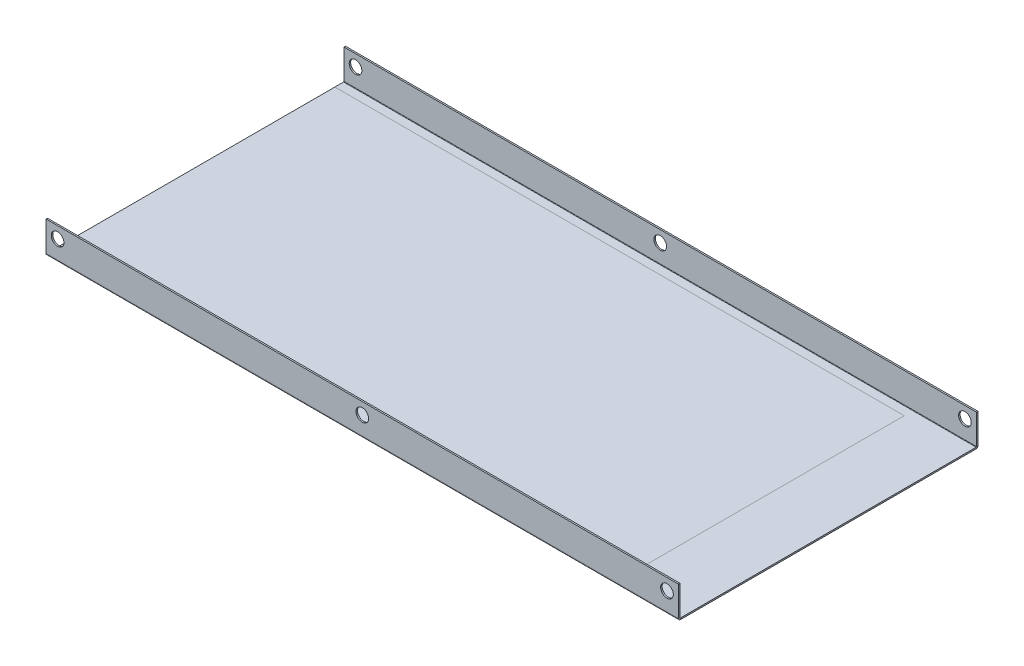
SolidWorks part; units mm, degrees
note: The reader was unsure of these and kept them because the rebuilt part matched: thickness of "基体-法兰1", "边线-法兰1", "钣金8", "钣金9", "钣金10", "钣金11"; flange length of "边线-法兰1".
material "1023 碳钢板 (SS)"
ref_plane "前视基准面" through (0, 0, 0) normal (0, 0, 1) x (1, 0, 0)
ref_plane "上视基准面" through (0, 0, 0) normal (0, 1, 0) x (1, 0, 0)
ref_plane "右视基准面" through (0, 0, 0) normal (1, 0, 0) x (0, 0, -1)
sketch "草图1" plane through (0, 0, 0) normal (0, 1, 0) x (1, 0, 0)
  line L1 (-150, -71) -> (150, -71)
  line L2 (-150, -71) -> (-150, 71)
  line L3 (-150, 71) -> (150, 71)
  line L4 (150, -71) -> (150, 71)
  line L5 (-150, -71) -> (150, 71) construction
  line L6 (-150, 71) -> (150, -71) construction
  point P0 (0, 0)
  dimension "D1" = 142
  dimension "D2" = 300
base flange "基体-法兰1" sketch "草图1" thickness 0.7 reverse thickness direction no parameters "D1"=0.2
edge flange "边线-法兰1" sketch "草图15" flange profiles "草图15", "草图16" flange angle 90 flange length 15 flange position material inside bend radius 0.2 thickness 0.7 relief rectangular parameters "D6"=10, "D8"=1
sketch "草图15" plane through (0, 0, -71) normal (0, 0, -1) x (-1, 0, 0)
  line L2 (-150, 0) -> (-150, 14.3)
  line L3 (-150, 14.3) -> (150, 14.3)
  line L4 (150, 14.3) -> (150, 0)
  line L11 (-150, 0) -> (150, 0) construction
  line L12 (-150, 0) -> (150, 0)
sketch "草图16" plane through (0, 0, 71) normal (0, 0, 1) x (1, 0, 0)
  line L2 (-150, 0) -> (-150, 14.3)
  line L3 (-150, 14.3) -> (150, 14.3)
  line L4 (150, 14.3) -> (150, 0)
  line L7 (-150, 0) -> (150, 0) construction
  line L8 (-150, 0) -> (150, 0)
bend "边线折弯1" bend radius 0.2 bend angle 90 parameters "D5"=1
bend "边线折弯2" bend radius 0.2 bend angle 90 parameters "D5"=2
sketch "草图18" plane through (0, 0, -71) normal (0, 0, -1) x (-1, 0, 0)
  line L0 (-150, 14.3) -> (-150, 0.2) construction
  line L1 (150, 14.3) -> (-150, 14.3) construction
  line L2 (0, 14.3) -> (0, 0) construction
  circle A0 centre (-144.5, 8.8) radius 3
  circle A1 centre (0, 8.8) radius 3
  circle A2 centre (144.5, 8.8) radius 3
  dimension "D1" = 5.5
  dimension "D3" = 6
  dimension "D4" = 6
  dimension "D2" = 5.5
  dimension "D5" = 5.5
extrude "切除-拉伸1" cut sketch "草图18" against normal blind 10
sketch "草图20" plane through (0, 0, 71) normal (0, 0, 1) x (1, 0, 0)
  line L0 (150, 14.3) -> (-150, 14.3) construction
  line L1 (-150, 14.3) -> (-150, 0.2) construction
  line L2 (0, 14.3) -> (0, 0) construction
  circle A0 centre (-144.5, 8.8) radius 3
  circle A1 centre (0, 8.8) radius 3
  circle A2 centre (144.5, 8.8) radius 3
  dimension "D1" = 6
  dimension "D2" = 5.5
  dimension "D3" = 5.5
  dimension "D4" = 6
  dimension "D5" = 5.5
extrude "切除-拉伸2" cut sketch "草图20" against normal blind 10
sketch "草图21" plane through (0, 0, 0) normal (0, 1, 0) x (1, 0, 0)
  line L0 (-150, 66) -> (120, 66)
  line L1 (-150, -71) -> (-150, 71) construction
  line L2 (120, 66) -> (120, -66)
  line L3 (120, -66) -> (-150, -66)
  line L4 (-150, 70.1) -> (-150, -70.1) construction
  line L5 (-150, 71) -> (150, 71) construction
  line L6 (150, -70.1) -> (150, 70.1) construction
  line L7 (150, -71) -> (-150, -71) construction
  dimension "D1" = 5
  dimension "D2" = 30
  dimension "D3" = 5
split "分割1" trim tools "草图21" bodies to split 111 resulting bodies 112 113
sketch "折弯-线3" plane through (0, 0, 0) normal (0, 1, 0) x (1, 0, 0)
sketch "边界框3" plane through (0, 0, 0) normal (0, 1, 0) x (1, 0, 0)
sheet metal parameters "钣金8" thickness 0.7 parameters "D1"=0.2
flat pattern "平板型式8" [suppressed]
sketch "折弯-线4" plane through (0, 0, 0) normal (0, 1, 0) x (1, 0, 0)
sketch "边界框4" [suppressed] plane through (0, 0, 0) normal (0, 1, 0) x (1, 0, 0)
sheet metal parameters "钣金9" thickness 0.7 parameters "D1"=0.2, "D7"=0.01
flat pattern "平板型式8" [suppressed]
sketch "折弯-线4" plane through (0, 0, 0) normal (0, 1, 0) x (1, 0, 0)
sketch "边界框4" [suppressed] plane through (0, 0, 0) normal (0, 1, 0) x (1, 0, 0)
bend of the flat pattern "展平-<边线折弯1>1"
bend of the flat pattern "展平-<边线折弯2>1"
sheet metal parameters "钣金10" thickness 0.7 parameters "D1"=0.2, "D7"=0.01
flat pattern "平板型式8" [suppressed]
sketch "折弯-线4" plane through (0, 0, 0) normal (0, 1, 0) x (1, 0, 0)
sketch "边界框4" [suppressed] plane through (0, 0, 0) normal (0, 1, 0) x (1, 0, 0)
bend of the flat pattern "展平-<边线折弯1>1"
bend of the flat pattern "展平-<边线折弯2>1"
sheet metal parameters "钣金11" thickness 0.7 parameters "D1"=0.2, "D7"=0.01
flat pattern "平板型式8" [suppressed]
sketch "折弯-线4" plane through (0, 0, 0) normal (0, 1, 0) x (1, 0, 0)
sketch "边界框4" [suppressed] plane through (0, 0, 0) normal (0, 1, 0) x (1, 0, 0)
bend of the flat pattern "展平-<边线折弯1>1"
bend of the flat pattern "展平-<边线折弯2>1"
sheet metal parameters "钣金12" thickness 0.01 parameters "D1"=0.2
flat pattern "平板型式12"
sketch "折弯-线5" plane through (0, 0, 0) normal (0, 1, 0) x (1, 0, 0)
sketch "边界框5" [suppressed] plane through (0, 0, 0) normal (0, 1, 0) x (1, 0, 0)
sheet metal parameters "钣金13" thickness 0.01 parameters "D1"=0.2
flat pattern "平板型式13" [suppressed]
sketch "折弯-线6" plane through (0, 0, 0) normal (0, 1, 0) x (1, 0, 0)
sketch "边界框6" [suppressed] plane through (0, 0, 0) normal (0, 1, 0) x (1, 0, 0)
bend of the flat pattern "展平-<边线折弯1>2"
bend of the flat pattern "展平-<边线折弯2>2"
